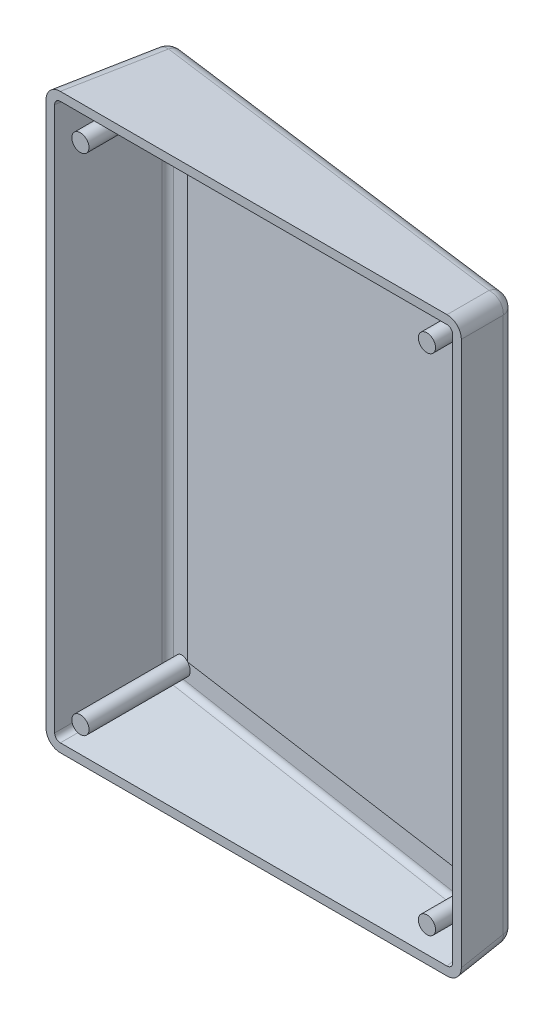
SolidWorks part; units mm, degrees
ref_plane "Спереди" through (0, 0, 0) normal (0, 0, 1) x (1, 0, 0)
ref_plane "Сверху" through (0, 0, 0) normal (0, 1, 0) x (1, 0, 0)
ref_plane "Справа" through (0, 0, 0) normal (1, 0, 0) x (0, 0, -1)
sketch "Sketch1" plane through (0, 0, 0) normal (0, 0, 1) x (1, 0, 0)
  line L0 (0, 100) -> (0, -100) construction
  line L1 (72.5, -100) -> (-72.5, -100)
  line L2 (72.5, -100) -> (72.5, 100)
  line L3 (72.5, 100) -> (-72.5, 100)
  line L4 (-72.5, -100) -> (-72.5, 100)
  line L5 (-72.5, 0) -> (72.5, 0) construction
  dimension "D1" = 145
  dimension "D2" = 200
extrude "Boss-Extrude1" add sketch "Sketch1" against normal blind 40 draft 5
sketch "Sketch2" plane through (0, 0, 0) normal (0, 1, 0) x (1, 0, 0)
  line L0 (-69.0005, 40) -> (70.7502, 20)
  line L1 (69.0005, 40) -> (72.5, 0) construction
  line L2 (69.0005, 40) -> (-69.0005, 40) construction
  line L3 (69.0005, 40) -> (70.7502, 20)
  line L4 (69.0005, 40) -> (-69.0005, 40)
extrude "Cut-Extrude1" cut sketch "Sketch2" against normal through all and the other way through all
fillet "Fillet1" radius 5 4 edges at (71.6251, -99.1251, -10) (-70.7502, -98.2502, -20) (71.6251, 99.1251, -10) (-70.7502, 98.2502, -20)
fillet "Fillet2" radius 5 8 edges at (-67.5619, 95.0619, -39.7941) (-69.0005, 0, -40) (-67.5619, -95.0619, -39.7941) (0.8125, -97.3746, -30.0089) (69.2752, -96.7752, -20.2111) (70.7502, 0, -20) (69.2752, 96.7752, -20.2111) (0.8125, 97.3746, -30.0089)
sketch "Sketch3" plane through (4.2248, 0, -29.5206) normal (0.1417, 0, -0.9899) x (-0.9899, 0, -0.1417)
  line L0 (-63.2364, 0) -> (68.6891, 0) construction
  line L1 (-54.2737, 82.5) -> (59.7263, 82.5)
  line L2 (-54.2737, 82.5) -> (-54.2737, -82.5)
  line L3 (-54.2737, -82.5) -> (59.7263, -82.5)
  line L4 (59.7263, 82.5) -> (59.7263, -82.5)
  line L5 (-63.2364, 93.615) -> (-63.2364, -93.615) construction
  line L6 (68.6891, -91.9799) -> (68.6891, 91.9799) construction
  line L7 (2.7263, 92.7974) -> (2.7263, -92.7974) construction
  line L8 (68.6891, 91.9799) -> (-63.2364, 93.615) construction
  line L9 (-63.2364, -93.615) -> (68.6891, -91.9799) construction
  dimension "D1" = 165
  dimension "D2" = 114
extrude "Cut-Extrude2" cut sketch "Sketch3" against normal blind 0.5 draft 5
shell "Shell1" thickness 3 removed face at (0, 0, 0)
sketch "Sketch4" plane through (0, 0, 0) normal (0, 0, 1) x (1, 0, 0)
  circle A0 centre (-60.5, 88) radius 3
  circle A1 centre (60.5, 88) radius 3
  circle A2 centre (-60.5, -88) radius 3
  circle A3 centre (60.5, -88) radius 3
  dimension "D1" = 6
extrude "Boss-Extrude2" add sketch "Sketch4" against normal up to surface (35.3236 mm away) up to face at (1.1009, 0, -26.9371)
sketch "Sketch5" plane through (4.1539, 0, -29.0256) normal (0.1417, 0, -0.9899) x (-0.9899, 0, -0.1417)
  line L0 (-54.2737, 0) -> (59.7263, 0) construction
  line L2 (2.7263, 82.4563) -> (2.7263, -82.4563) construction
  line L3 (-54.2737, 82.5) -> (-54.2737, -82.5) construction
  line L4 (59.7263, -82.5) -> (59.7263, 82.5) construction
  line L5 (59.6826, 82.4563) -> (-54.2299, 82.4563) construction
  line L6 (-54.2299, -82.4563) -> (59.6826, -82.4563) construction
